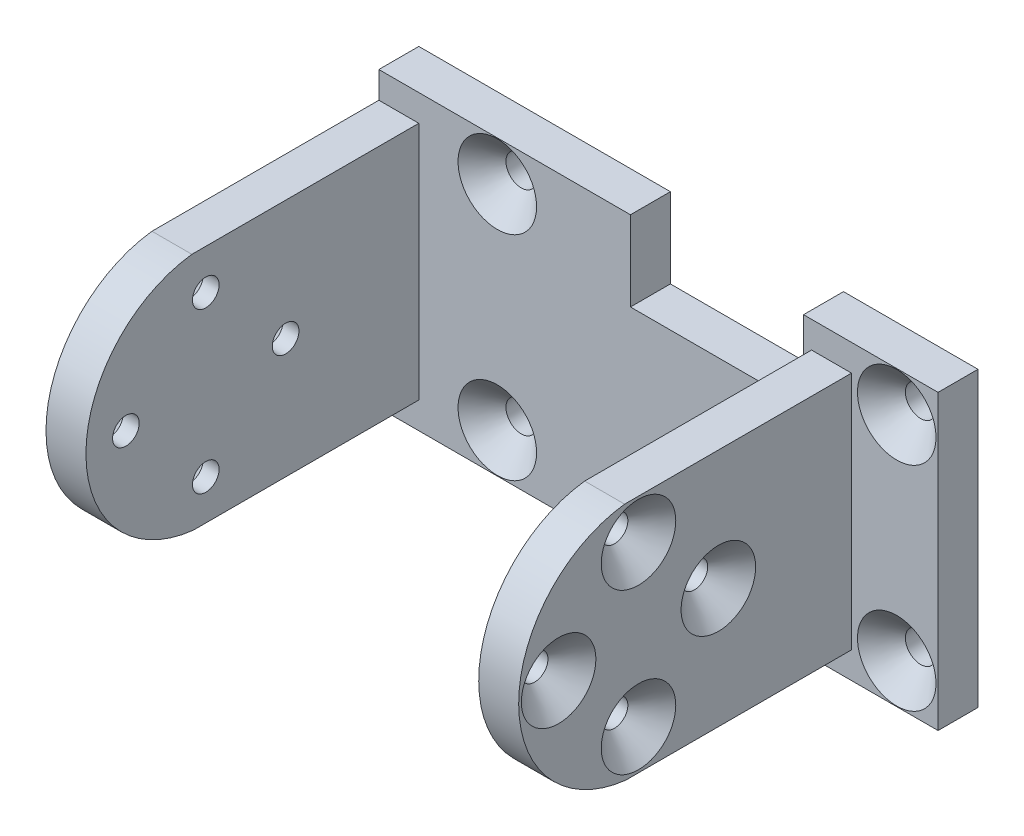
SolidWorks part; units mm, degrees
ref_plane "Front Plane" through (0, 0, 0) normal (0, 0, 1) x (1, 0, 0)
ref_plane "Top Plane" through (0, 0, 0) normal (0, 1, 0) x (1, 0, 0)
ref_plane "Right Plane" through (0, 0, 0) normal (1, 0, 0) x (0, 0, -1)
ref_plane "Plane1" through (0, 0, 163.527) normal (0, 0, 1) x (1, 0, 0)
sketch "Sketch1" plane through (0, 0, 163.527) normal (0, 0, 1) x (1, 0, 0)
  line L0 (36.2066, 229.3346) -> (-5.7934, 229.3346)
  line L1 (-5.7934, 229.3346) -> (-5.7934, 207.3346)
  line L2 (-5.7934, 207.3346) -> (36.2066, 207.3346)
  line L3 (36.2066, 207.3346) -> (36.2066, 229.3346)
extrude "Boss-Extrude1" add sketch "Sketch1" against normal blind 3
sketch "Sketch2" plane through (0, 0, 160.527) normal (0, 0, -1) x (-1, 0, 0)
  line L0 (-13.1033, 229.3346) -> (-26.1033, 229.3346)
  line L1 (-26.1033, 229.3346) -> (-26.1033, 223.3346)
  line L2 (-26.1033, 223.3346) -> (-13.1033, 223.3346)
  line L3 (-13.1033, 223.3346) -> (-13.1033, 229.3346)
extrude "Cut-Extrude1" cut sketch "Sketch2" against normal through all
sketch "Sketch3" plane through (0, 0, 160.527) normal (0, 0, -1) x (-1, 0, 0)
  line L0 (-26.1033, 207.3346) -> (-13.1033, 207.3346)
  line L1 (-13.1033, 207.3346) -> (-13.1033, 213.3346)
  line L2 (-13.1033, 213.3346) -> (-26.1033, 213.3346)
  line L3 (-26.1033, 213.3346) -> (-26.1033, 207.3346)
extrude "Cut-Extrude2" cut sketch "Sketch3" against normal through all
ref_plane "Plane2" through (-5.7934, 0, 0) normal (-1, 0, 0) x (0, -1, 0)
sketch "Sketch4" plane through (-5.7934, 0, 0) normal (-1, 0, 0) x (0, -1, 0)
  line L0 (-227.3346, 180.5701) -> (-227.3346, 163.527)
  line L1 (-227.3346, 163.527) -> (-209.3346, 163.527)
  line L2 (-209.3346, 163.527) -> (-209.3346, 180.4739)
  arc A0 (-209.3346, 180.4739) -> (-227.3346, 180.5701) centre (-218.3403, 179.465) ccw
extrude "Boss-Extrude2" add sketch "Sketch4" against normal blind 3
ref_plane "Plane3" through (29.7066, 0, 0) normal (1, 0, 0) x (0, 0, -1)
sketch "Sketch5" plane through (29.7066, 0, 0) normal (1, 0, 0) x (0, 0, -1)
  line L0 (-180.4739, 209.3346) -> (-163.527, 209.3346)
  line L1 (-163.527, 209.3346) -> (-163.527, 227.3346)
  line L2 (-163.527, 227.3346) -> (-180.5701, 227.3346)
  arc A0 (-180.5701, 227.3346) -> (-180.4739, 209.3346) centre (-179.465, 218.3403) ccw
extrude "Boss-Extrude3" add sketch "Sketch5" against normal blind 3
hole_wizard "Ø2.0 (2) Diameter Hole1" positions "Sketch7" profile "Sketch6" hole size "Ø2.0" standard "ANSI Metric"
sketch "Sketch7" plane through (29.7066, 0, 0) normal (1, 0, 0) x (0, 0, -1)
  point P0 (-179.5272, 224.3342)
  point P1 (-185.527, 218.3344)
  point P2 (-179.5272, 212.3346)
  point P3 (-173.5274, 218.3344)
sketch "Sketch6" plane through (29.7066, 224.3342, 179.5272) normal (0, 1, 0) x (0, 0, -1)
  line L0 (0, 0) -> (0, 3)
  line L1 (0, 3) -> (1, 3)
  line L2 (1, 3) -> (1, 1.8)
  line L3 (1, 1.8) -> (2.8, 0)
  line L5 (2.8, 0) -> (0, 0)
  line L6 (-1, 1.8) -> (-2.8, 0) construction
  line L11 (0, -6.35) -> (0, 107.95) construction
  dimension "Thru Hole Dia." = 2
  dimension "Thru Hole Depth" = 3
  dimension "Near C'Sink Dia." = 5.6
  dimension "Near C'Sink Angle" = 90
hole_wizard "CSK for M2 Flat Head Machine Screw1" positions "Sketch9" profile "Sketch8" countersink size "M2" standard "ANSI Metric"
sketch "Sketch9" plane through (0, 0, 163.527) normal (0, 0, 1) x (1, 0, 0)
  point P0 (3.1033, 226.327)
  point P1 (3.1033, 210.327)
  point P2 (33.1033, 210.327)
  point P3 (33.1033, 226.327)
sketch "Sketch8" plane through (3.1033, 226.327, 163.527) normal (1, 0, 0) x (0, -1, 0)
  line L0 (0, 0) -> (0, 3)
  line L1 (0, 3) -> (1.15, 3)
  line L2 (1.15, 3) -> (1.15, 1.8)
  line L3 (1.15, 1.8) -> (2.95, 0)
  line L5 (2.95, 0) -> (0, 0)
  line L6 (-1.15, 1.8) -> (-2.95, 0) construction
  line L11 (0, -6.35) -> (0, 107.95) construction
  dimension "Thru Hole Dia." = 2.3
  dimension "Thru Hole Depth" = 3
  dimension "Near C'Sink Dia." = 5.9
  dimension "Near C'Sink Angle" = 90
hole_wizard "Ø2.0 (2) Diameter Hole2" positions "Sketch11" profile "Sketch10" hole size "Ø2.0" standard "ANSI Metric"
sketch "Sketch11" plane through (-5.7934, 0, 0) normal (-1, 0, 0) x (0, 0, 1)
  point P0 (179.5272, 224.3342)
  point P1 (185.527, 218.3344)
  point P2 (179.5272, 212.3346)
  point P3 (173.5274, 218.3344)
sketch "Sketch10" plane through (-5.7934, 224.3342, 179.5272) normal (0, 1, 0) x (0, 0, 1)
  line L0 (0, 0) -> (0, 42)
  line L1 (0, 42) -> (1, 42)
  line L2 (1, 42) -> (1, 1.8)
  line L3 (1, 1.8) -> (2.8, 0)
  line L5 (2.8, 0) -> (0, 0)
  line L6 (-1, 1.8) -> (-2.8, 0) construction
  line L11 (0, -6.35) -> (0, 107.95) construction
  dimension "Thru Hole Dia." = 2
  dimension "Thru Hole Depth" = 42
  dimension "Near C'Sink Dia." = 5.6
  dimension "Near C'Sink Angle" = 90
